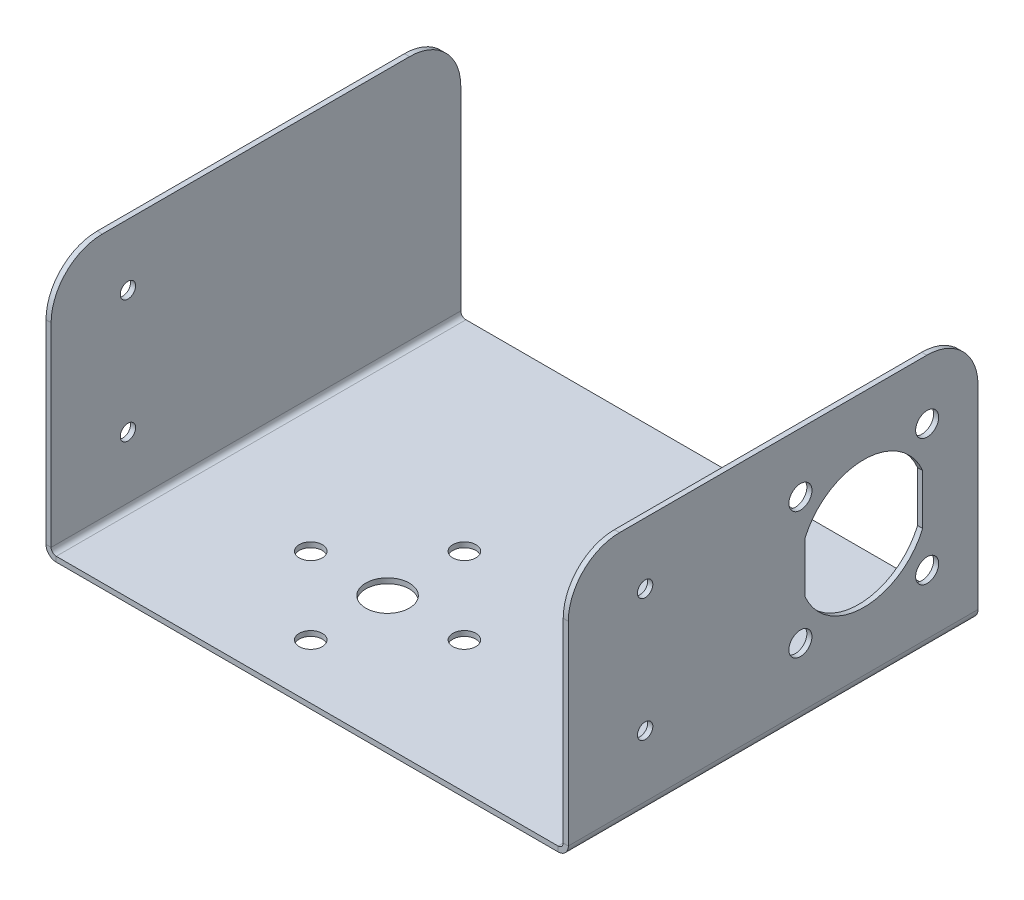
SolidWorks part; units mm, degrees
note: The reader was unsure of these and kept them because the rebuilt part matched: flange length of "Edge-Flange1", "Edge-Flange2".
material "AISI 1020"
ref_plane "Front Plane" through (0, 0, 0) normal (0, 0, 1) x (1, 0, 0)
ref_plane "Top Plane" through (0, 0, 0) normal (0, 1, 0) x (1, 0, 0)
ref_plane "Right Plane" through (0, 0, 0) normal (1, 0, 0) x (0, 0, -1)
sketch "Sketch1" plane through (0, 0, 0) normal (0, 1, 0) x (1, 0, 0)
  line L1 (0, 0) -> (100, 0)
  line L2 (0, 0) -> (0, 80)
  line L3 (0, 80) -> (100, 80)
  line L4 (100, 0) -> (100, 80)
  dimension "D1" = 100
  dimension "D2" = 80
base flange "Base-Flange1" sketch "Sketch1" thickness 1 reverse thickness direction no parameters "D1"=1
edge flange "Edge-Flange1" sketch "Sketch8" flange angle 90 flange length 50 flange position material outside bend radius 1 thickness 1 parameters "D6"=10
sketch "Sketch8" plane through (100, 0, 0) normal (1, 0, 0) x (0, 0, -1)
  line L2 (0, 0) -> (0, 49)
  line L3 (0, 49) -> (80, 49)
  line L4 (80, 49) -> (80, 0)
  line L7 (0, 0) -> (80, 0) construction
  line L8 (0, 0) -> (80, 0)
bend "EdgeBend1" bend radius 1 bend angle 90 parameters "D5"=1
edge flange "Edge-Flange2" sketch "Sketch11" flange angle 90 flange length 50 flange position material outside bend radius 1 thickness 1 parameters "D6"=10
sketch "Sketch11" plane through (0, 0, 0) normal (-1, 0, 0) x (0, 0, 1)
  line L0 (-80, 0) -> (0, 0) construction
  line L1 (-80, 0) -> (0, 0)
  line L2 (-80, 0) -> (-80, 49)
  line L3 (-80, 49) -> (0, 49)
  line L4 (0, 49) -> (0, 0)
bend "EdgeBend2" bend radius 1 bend angle 90 parameters "D5"=2
fillet "Fillet1" radius 10 4 edges at (100.5, 49, -80) (-0.5, 49, -80) (100.5, 49, 0) (-0.5, 49, 0)
extrude "Cut-Extrude1" cut sketch "Sketch12" against normal blind 10
sketch "Sketch12" plane through (101, 81.3735, -102.5325) normal (1, 0, 0) x (0, 0, 1)
  line L0 (22.5325, 32.3735) -> (56.3325, 52.6535) construction
  line L1 (102.5325, 80.3735) -> (22.5325, 80.3735) construction
  line L2 (22.5325, 80.3735) -> (102.5325, 32.3735) construction
  line L3 (102.5325, 56.3735) -> (62.5325, 56.3735) construction
  line L6 (44.8325, 56.3735) -> (28.0954, 73.1106) construction
  line L7 (33.3325, 61.2725) -> (33.3325, 51.4745)
  line L8 (56.3325, 61.2725) -> (56.3325, 51.4745)
  line L9 (62.5325, 56.3735) -> (102.5325, 80.3735) construction
  line L10 (56.3325, 56.3735) -> (22.5325, 56.3735) construction
  arc A0 (33.3325, 51.4745) -> (56.3325, 51.4745) centre (44.8325, 56.3735) ccw
  arc A1 (56.3325, 61.2725) -> (33.3325, 61.2725) centre (44.8325, 56.3735) ccw
  circle A2 centre (32.4581, 68.7479) radius 2.25
  circle A3 centre (57.2068, 68.7479) radius 2.25
  circle A4 centre (57.2068, 43.9992) radius 2.25
  circle A5 centre (32.4581, 43.9992) radius 2.25
  point P34 (44.8325, 56.3735)
extrude "Cut-Extrude3" cut sketch "Sketch14" against normal blind 10
sketch "Sketch14" plane through (82.6867, -1, -102.5325) normal (0, -1, 0) x (-1, 0, 0)
  line L0 (42.6867, -22.5325) -> (42.6867, -102.5325) construction
  line L3 (42.6867, -91.8325) -> (42.6867, -61.8325) construction
  line L4 (27.6867, -76.8325) -> (57.6867, -76.8325) construction
  line L5 (81.6867, -102.5325) -> (-16.3133, -102.5325) construction
  circle A0 centre (42.6867, -76.8325) radius 4.25
  circle A5 centre (57.6867, -76.8325) radius 2.25
  circle A6 centre (42.6867, -61.8325) radius 2.25
  circle A7 centre (27.6867, -76.8325) radius 2.25
  circle A8 centre (42.6867, -91.8325) radius 2.25
  point P11 (42.6867, -76.8325)
  point P17 (42.6867, -76.8325)
  point P21 (42.6867, -76.8325)
extrude "Cut-Extrude4" cut sketch "Sketch15" against normal through all
sketch "Sketch15" plane through (101, 81.3735, -102.5325) normal (1, 0, 0) x (0, 0, 1)
  line L0 (87.5325, 80.3735) -> (87.5325, 32.3735) construction
  circle A0 centre (87.5325, 44.3735) radius 1.5
  circle A1 centre (87.5325, 68.3735) radius 1.5
sketch "Bend-Lines1" [suppressed] plane through (0, 0, 0) normal (0, 1, 0) x (1, 0, 0)
sketch "Bounding-Box1" [suppressed] plane through (0, 0, 0) normal (0, 1, 0) x (1, 0, 0)
sheet metal parameters "Sheet-Metal1" thickness 1 parameters "D1"=1
flat pattern "Flat-Pattern1" [suppressed]
sketch "Bend-Lines2" plane through (0, 0, 0) normal (0, 1, 0) x (1, 0, 0)
sketch3d "Bounding-Box2" [suppressed]
  line L0 (0, 0, 0) -> (0, 80, 0) construction
  line L1 (-55, 0, 0) -> (-55, 80, 0) construction
  line L2 (0, 0, 0) -> (-55, 0, 0) construction
  line L3 (0, 80, 0) -> (-55, 80, 0) construction
sheet metal parameters "Sheet-Metal2" thickness 1 parameters "D1"=1
flat pattern "Flat-Pattern1"
sketch "Bend-Lines2" plane through (0, 0, 0) normal (0, 1, 0) x (1, 0, 0)
  line L0 (54.1781, 0) -> (54.1781, 80) construction
  line L1 (54.1781, 0) -> (54.1781, 80) construction
sketch3d "Bounding-Box2" [suppressed]
  line L0 (103.3562, 80, 0) -> (0, 80, 0) construction
  line L1 (103.3562, 0, 0) -> (0, 0, 0) construction
  line L2 (103.3562, 80, 0) -> (103.3562, 0, 0) construction
  line L3 (0, 80, 0) -> (0, 0, 0) construction
bend of the flat pattern "Flatten-<EdgeBend1>1"
sheet metal parameters "Sheet-Metal3" thickness 1 parameters "D1"=1
flat pattern "Flat-Pattern1"
sketch "Bend-Lines2" plane through (0, 0, 0) normal (0, 1, 0) x (1, 0, 0)
  line L0 (55.1781, 0) -> (55.1781, 80) construction
  line L1 (55.1781, 0) -> (55.1781, 80) construction
  line L2 (-0.1781, 80) -> (-0.1781, 0) construction
  line L3 (-0.1781, 80) -> (-0.1781, 0) construction
sketch3d "Bounding-Box2" [suppressed]
  line L0 (-49.3562, 80, 0) -> (104.3562, 80, 0) construction
  line L1 (-49.3562, 0, 0) -> (104.3562, 0, 0) construction
  line L2 (-49.3562, 80, 0) -> (-49.3562, 0, 0) construction
  line L3 (104.3562, 80, 0) -> (104.3562, 0, 0) construction
bend of the flat pattern "Flatten-<EdgeBend1>1"
bend of the flat pattern "Flatten-<EdgeBend2>1"
sheet metal parameters "Sheet-Metal4" thickness 1 parameters "D1"=1
flat pattern "Flat-Pattern1"
sketch "Bend-Lines2" plane through (0, 0, 0) normal (0, 1, 0) x (1, 0, 0)
  line L0 (100.1781, 0) -> (100.1781, 80) construction
  line L1 (100.1781, 0) -> (100.1781, 80) construction
  line L2 (-0.1781, 80) -> (-0.1781, 0) construction
  line L3 (-0.1781, 80) -> (-0.1781, 0) construction
sketch3d "Bounding-Box2" [suppressed]
  line L0 (-49.3562, 80, 0) -> (149.3562, 80, 0) construction
  line L1 (-49.3562, 0, 0) -> (149.3562, 0, 0) construction
  line L2 (-49.3562, 80, 0) -> (-49.3562, 0, 0) construction
  line L3 (149.3562, 80, 0) -> (149.3562, 0, 0) construction
bend of the flat pattern "Flatten-<EdgeBend1>1"
bend of the flat pattern "Flatten-<EdgeBend2>1"
sheet metal parameters "Sheet-Metal6" thickness 1 parameters "D1"=1
flat pattern "Flat-Pattern1"
sketch "Bend-Lines2" plane through (0, 0, 0) normal (0, 1, 0) x (1, 0, 0)
  line L0 (100.1781, 0) -> (100.1781, 100) construction
  line L1 (100.1781, 0) -> (100.1781, 100) construction
  line L2 (-0.1781, 100) -> (-0.1781, 0) construction
  line L3 (-0.1781, 100) -> (-0.1781, 0) construction
sketch3d "Bounding-Box2" [suppressed]
  line L0 (-49.3562, 100, 0) -> (149.3562, 100, 0) construction
  line L1 (-49.3562, 0, 0) -> (149.3562, 0, 0) construction
  line L2 (-49.3562, 100, 0) -> (-49.3562, 0, 0) construction
  line L3 (149.3562, 100, 0) -> (149.3562, 0, 0) construction
bend of the flat pattern "Flatten-<EdgeBend1>1"
bend of the flat pattern "Flatten-<EdgeBend2>1"
sheet metal parameters "Sheet-Metal7" thickness 1 parameters "D1"=1
flat pattern "Flat-Pattern1"
sketch "Bend-Lines2" plane through (0, 0, 0) normal (0, 1, 0) x (1, 0, 0)
  line L0 (100.1781, 0) -> (100.1781, 80) construction
  line L1 (100.1781, 0) -> (100.1781, 80) construction
  line L2 (-0.1781, 80) -> (-0.1781, 0) construction
  line L3 (-0.1781, 80) -> (-0.1781, 0) construction
sketch3d "Bounding-Box2" [suppressed]
  line L0 (-49.3562, 80, 0) -> (149.3562, 80, 0) construction
  line L1 (-49.3562, 0, 0) -> (149.3562, 0, 0) construction
  line L2 (-49.3562, 80, 0) -> (-49.3562, 0, 0) construction
  line L3 (149.3562, 80, 0) -> (149.3562, 0, 0) construction
bend of the flat pattern "Flatten-<EdgeBend1>1"
bend of the flat pattern "Flatten-<EdgeBend2>1"
